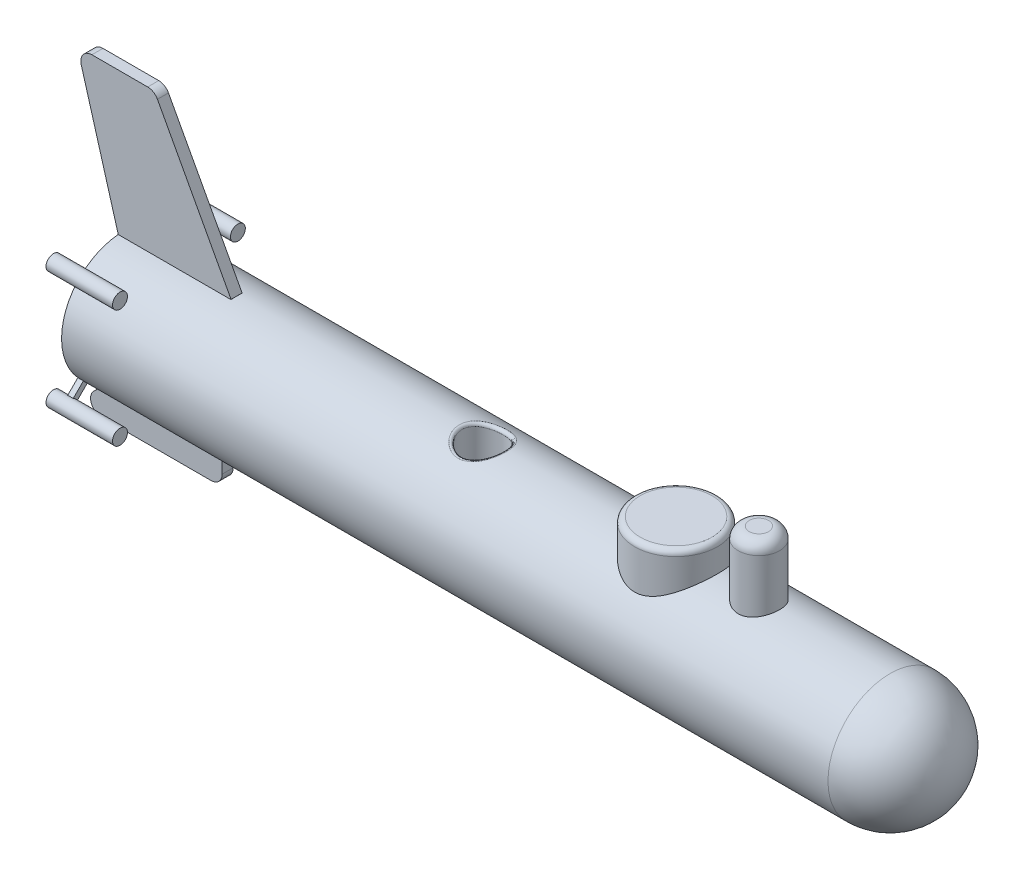
SolidWorks part; units mm, degrees
ref_plane "Спереди" through (0, 0, 0) normal (0, 0, 1) x (1, 0, 0)
ref_plane "Сверху" through (0, 0, 0) normal (0, 1, 0) x (1, 0, 0)
ref_plane "Справа" through (0, 0, 0) normal (1, 0, 0) x (0, 0, -1)
sketch "Эскиз1" plane through (0, 0, 0) normal (1, 0, 0) x (0, 0, -1)
  circle A0 centre (0, 0) radius 225
  dimension "D1" = 450
extrude "Бобышка-Вытянуть1" add sketch "Эскиз1" along normal mid plane 3000
fillet "Скругление1" radius 225 1 edges at (1500, 0, -225)
sketch "Эскиз3" plane through (0, 0, 0) normal (0, 1, 0) x (1, 0, 0)
  line L0 (-1500, 225) -> (-1500, -225) construction
  line L1 (-1500, 225) -> (-1500, -225)
  line L2 (-1500, 0) -> (1500, 0) construction
  arc A0 (1275, -225) -> (1275, 225) centre (1275, 0) ccw construction
  circle A1 centre (500, 0) radius 150
  circle A2 centre (800, 0) radius 75
  circle A3 centre (-200, 0) radius 75
  point P13 (0, 0)
  dimension "D1" = 300
  dimension "D3" = 150
  dimension "D5" = 150
  dimension "D2" = 1000
  dimension "D4" = 700
  dimension "D6" = 200
extrude "Бобышка-Вытянуть2" add sketch "Эскиз3" along normal blind 330 contours L2 A1 | A1 L2 region at (500, 0, -63.662) region at (500, 0, 63.662)
fillet "Скругление2" radius 20 1 edges at (500, 330, 150)
extrude "Бобышка-Вытянуть3" add sketch "Эскиз3<3>" along normal blind 450 contours L2 A2 | A2 L2 region at (800, 0, -31.831) region at (800, 0, 31.831)
sketch "Эскиз3<3>" plane through (0, 0, 0) normal (0, 1, 0) x (1, 0, 0) same geometry as "Эскиз3"
fillet "Скругление3" radius 40 1 edges at (800, 450, 75)
sketch "Эскиз4" plane through (0, 0, 0) normal (0, 0, 1) x (1, 0, 0)
  line L0 (-1500, 225) -> (-1648.3648, 740.1672)
  line L1 (-1648.3648, 740.1672) -> (-1369.2401, 740.1672)
  line L2 (-1369.2401, 740.1672) -> (-1091.3001, 225)
  line L3 (350, 225) -> (-1500, 225) construction
  line L4 (-1123.6157, -225) -> (-1123.6157, -379.3221)
  line L5 (-1500, -225) -> (1275, -225) construction
  line L6 (-1123.6157, -379.3221) -> (-1658.312, -379.3221)
  line L7 (-1658.312, -379.3221) -> (-1500, -225)
  line L8 (350, 225) -> (-1500, 225)
  line L9 (-1500, -225) -> (1275, -225)
  line L11 (-1500, 225) -> (-1091.3001, 225)
  line L12 (-1500, 225) -> (-1500, 182.6501)
  line L13 (-1500, 182.6501) -> (-1091.3001, 182.6501)
  line L14 (-1091.3001, 225) -> (-1091.3001, 182.6501)
  line L15 (-1123.6157, -225) -> (-1500, -225)
  line L16 (-1123.6157, -225) -> (-1123.6157, -172.9951)
  line L17 (-1123.6157, -172.9951) -> (-1500, -172.9951)
  line L18 (-1500, -225) -> (-1500, -172.9951)
extrude "Бобышка-Вытянуть4" add sketch "Эскиз4" along normal mid plane 40 contours L8 L2 L1 L0 | L9 L7 L6 L4 | L14 L8 L12 L13 | L18 L9 L16 L17 region at (-1395.5338, 466.4087, 0) region at (-1295.6501, 203.8251, 0) region at (-1353.6782, -306.6303, 0) region at (-1311.8078, -198.9976, 0)
extrude "Вырез-Вытянуть1" cut sketch "Эскиз3<4>" against normal through all both and the other way through all contours L2 A3 | A3 L2 region at (-200, 0, -31.831) region at (-200, 0, 31.831)
sketch "Эскиз3<4>" plane through (0, 0, 0) normal (0, 1, 0) x (1, 0, 0) same geometry as "Эскиз3"
fillet "Скругление4" radius 40 4 edges at (-1648.3648, 740.1672, 0) (-1369.2401, 740.1672, 0) (-1123.6157, -379.3221, 0) (-1658.312, -379.3221, 0)
fillet "Скругление5" radius 10 2 edges at (-212.817, -212.5189, -73.8967) (-187.183, 212.5189, -73.8967)
sketch "Эскиз5" plane through (-1500, 0, 0) normal (-1, 0, 0) x (0, 0, 1)
  line L0 (0, 0) -> (-213.389, 213.389) construction
  line L1 (0, 0) -> (0, 225) construction
  line L2 (20, 225) -> (-20, 225) construction
  line L3 (-151.8707, 166.0129) -> (-188.5838, 202.726)
  line L4 (-166.0129, 151.8707) -> (-202.726, 188.5838)
  line L5 (-166.0129, 151.8707) -> (-151.8707, 166.0129)
  arc A2 (-20, 224.1093) -> (-20, -224.1093) centre (0, 0) ccw construction
  arc A3 (-20, 224.1093) -> (-20, -224.1093) centre (0, 0) ccw
  circle A4 centre (-213.389, 213.389) radius 27
  point P1 (-158.9418, 158.9418)
  arc M5 (-20, 224.1093) -> (-20, -224.1093) centre (0, 0) ccw
  dimension "D2" = 77
  dimension "D3" = 20
  dimension "D4" = 54
  dimension "D1" = 45
extrude "Бобышка-Вытянуть5" add sketch "Эскиз5" against normal blind 20 contours A4 L4 L3 M5 region at (-1500, 176.8971, -176.8971)
extrude "Бобышка-Вытянуть6" add sketch "Эскиз5<3>" along normal blind 41 and the other way blind 200 contours A4 region at (-1500, 213.389, -213.389)
sketch "Эскиз5<3>" plane through (-1500, 0, 0) normal (-1, 0, 0) x (0, 0, 1) same geometry as "Эскиз5"
pattern_circular "Круговой массив1" count 4 every 90 about axis through (1500, 0, 0) along (-1, 0, 0) of "Бобышка-Вытянуть5", "Бобышка-Вытянуть6"
